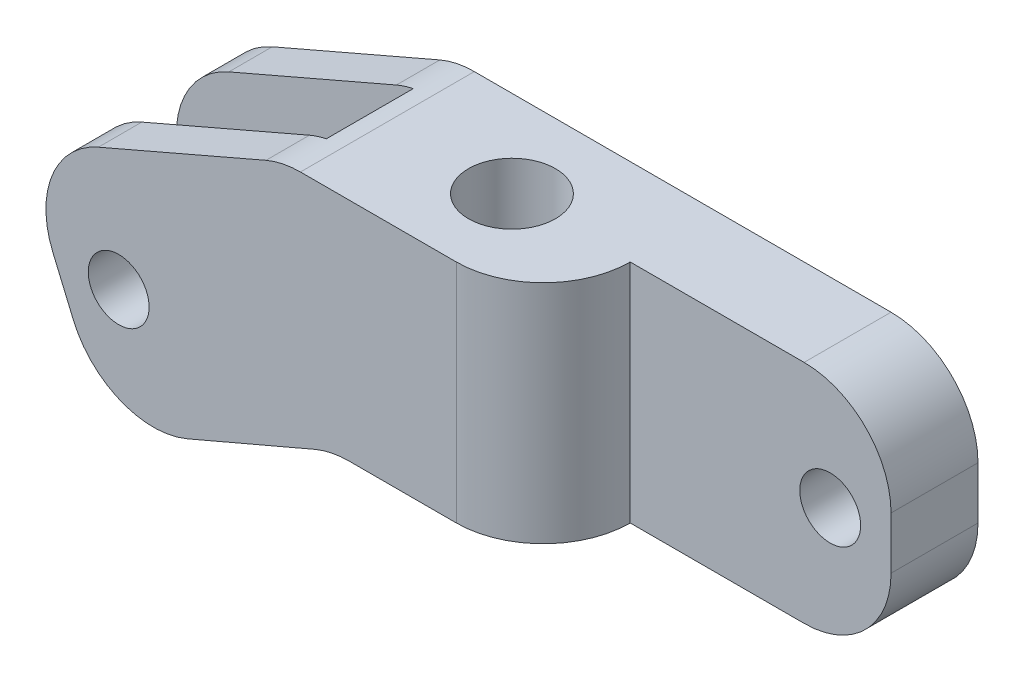
SolidWorks part; units mm, degrees
ref_plane "정면" through (0, 0, 0) normal (0, 0, 1) x (1, 0, 0)
ref_plane "윗면" through (0, 0, 0) normal (0, 1, 0) x (1, 0, 0)
ref_plane "우측면" through (0, 0, 0) normal (1, 0, 0) x (0, 0, -1)
sketch "스케치1" plane through (0, 0, 0) normal (0, 0, 1) x (1, 0, 0)
  line L0 (-6.9042, 6.5443) -> (-22.0507, -0.0005)
  line L1 (-22.0507, -0.0005) -> (-16.9734, -11.9679)
  line L2 (-4.1042, -6.4557) -> (-16.9734, -11.9679)
  line L3 (-4.1042, -6.4557) -> (23.0958, -6.4557)
  line L4 (23.0958, -6.4557) -> (23.0958, 6.5443)
  line L5 (-6.9042, 6.5443) -> (23.0958, 6.5443)
  line L6 (-19.5121, -5.9842) -> (8.0958, 6.5443) construction
  line L7 (23.0958, 0.0443) -> (-21.9471, 0.0443) construction
  circle A0 centre (-16.3239, -4.5374) radius 1.75
  circle A1 centre (19.5958, 0.0443) radius 1.75
  point P0 (-6.9042, 6.5443)
  point P1 (-4.1042, -6.4557)
  point P3 (0.0958, 0.0443)
  dimension "D9" = 3.5
  dimension "D10" = 3.5
  dimension "D1" = 13
  dimension "D2" = 30
  dimension "D3" = 27.2
  dimension "D4" = 16.5
  dimension "D5" = 14
  dimension "D6" = 13
  dimension "D7" = 3.5
  dimension "D8" = 3.5
extrude "보스-돌출1" add sketch "스케치1" along normal blind 10
ref_plane "평면1" through (0, 0, 5) normal (0, 0, 1) x (1, 0, 0)
sketch "스케치5" plane through (0, 0, 5) normal (0, 0, 1) x (1, 0, 0)
  line L0 (-6.9042, 6.5443) -> (23.0958, 6.5443)
  line L1 (23.0958, 6.5443) -> (23.1099, 6.5686)
  line L2 (-19.5121, -5.9842) -> (8.0958, 6.5443) construction
  line L3 (-22.0507, -0.0005) -> (23.0958, 0.0443) construction
  line L4 (8.0958, 6.5443) -> (8.0958, -6.4557)
  line L5 (-6.9042, 6.5443) -> (-4.1042, -6.4557)
  line L8 (-22.0507, -0.0005) -> (-16.9734, -11.9679)
  line L9 (-16.9734, -11.9679) -> (-4.1042, -6.4557)
  line L10 (-4.1042, -6.4557) -> (23.0958, -6.4557)
  line L11 (23.0958, -6.4557) -> (23.0958, 6.5443)
  line L13 (-6.9042, 6.5443) -> (-22.0507, -0.0005)
  circle A0 centre (-16.3239, -4.5374) radius 1.75
  circle A1 centre (19.5958, 0.0443) radius 1.75
sketch "스케치7" plane through (0, 0, 5) normal (0, 0, 1) x (1, 0, 0)
  line L0 (-22.0507, -0.0005) -> (-6.9042, 6.5443)
  line L1 (-6.9042, 6.5443) -> (-4.1042, -6.4557)
  line L2 (-4.1042, -6.4557) -> (-16.9734, -11.9679)
  line L3 (-16.9734, -11.9679) -> (-22.0507, -0.0005)
  line L4 (-22.0507, -0.0005) -> (-22.0505, -0.001)
sketch "스케치8" plane through (0, 0, 5) normal (0, 0, 1) x (1, 0, 0)
  line L0 (-22.0507, -0.0005) -> (-6.9042, 6.5443)
  line L1 (-6.9042, 6.5443) -> (-4.1042, -6.4557)
  line L2 (-4.1042, -6.4557) -> (-16.9734, -11.9679)
  line L3 (-16.9734, -11.9679) -> (-22.0507, -0.0005)
fillet "필렛8" radius 5 6 edges at (-16.9734, -11.9679, 5) (-4.1042, -6.4557, 5) (23.0958, -6.4557, 5) (23.0958, 6.5443, 5) (-22.0507, -0.0005, 5) (-6.9042, 6.5443, 5)
sketch "스케치9" plane through (0, 0, 5) normal (0, 0, 1) x (1, 0, 0)
  line L0 (-22.0507, -0.0005) -> (-6.9042, 6.5443)
  line L1 (-6.9042, 6.5443) -> (-4.1042, -6.4557)
  line L2 (-4.1042, -6.4557) -> (-16.9734, -11.9679)
  line L3 (-16.9734, -11.9679) -> (-22.0507, -0.0005)
extrude "컷-돌출7" cut sketch "스케치9" against normal blind 2.5
sketch "스케치10" plane through (0, 0, 5) normal (0, 0, 1) x (1, 0, 0)
  line L0 (-22.0507, -0.0005) -> (-6.9042, 6.5443)
  line L1 (-6.9042, 6.5443) -> (-4.1042, -6.4557)
  line L2 (-4.1042, -6.4557) -> (-16.9734, -11.9679)
  line L3 (-16.9734, -11.9679) -> (-22.0507, -0.0005)
extrude "컷-돌출8" cut sketch "스케치10" along normal blind 2.5
sketch "스케치11" plane through (0, 0, 5) normal (0, 0, 1) x (1, 0, 0)
  line L0 (8.0958, 6.5443) -> (23.1099, 6.5686)
  line L1 (23.1099, 6.5686) -> (23.0958, -6.4557)
  line L2 (23.0958, -6.4557) -> (8.0958, -6.4557)
  line L3 (8.0958, -6.4557) -> (8.0958, 6.5443)
extrude "컷-돌출10" cut sketch "스케치11" along normal blind 5
fillet "필렛11" radius 5 1 edges at (8.0958, 0.0443, 10)
ref_plane "평면2" through (0, 6.5443, 0) normal (0, 1, 0) x (1, 0, 0)
sketch "스케치12" plane through (0, 6.5443, 0) normal (0, 1, 0) x (1, 0, 0)
  line L0 (-20.5079, 0) -> (-20.5079, -10) construction
  line L1 (-20.5079, 0) -> (23.0958, 0) construction
  line L2 (23.0958, 0) -> (23.0958, -5) construction
  line L3 (-4.1042, -5) -> (23.0958, -5) construction
  line L4 (23.0958, -5) -> (-20.5079, -5) construction
  circle A0 centre (1.2939, -5) radius 2.5
extrude "컷-돌출11" cut sketch "스케치12" against normal blind 10
